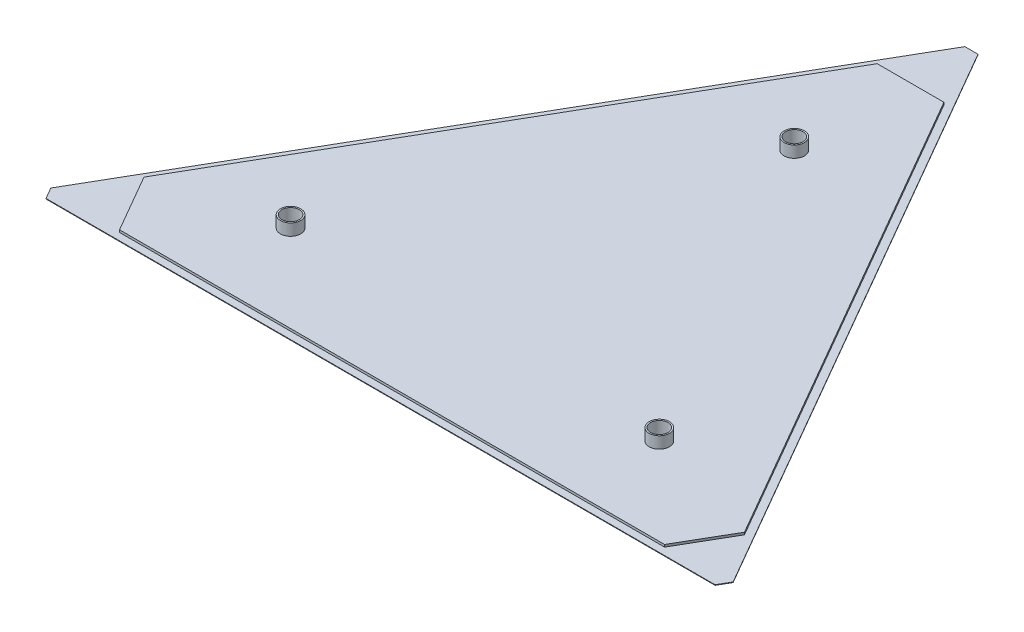
SolidWorks part; units mm, degrees
ref_plane "Front Plane" through (0, 0, 0) normal (0, 0, 1) x (1, 0, 0)
ref_plane "Top Plane" through (0, 0, 0) normal (0, 1, 0) x (1, 0, 0)
ref_plane "Right Plane" through (0, 0, 0) normal (1, 0, 0) x (0, 0, -1)
sketch "Sketch1" plane through (0, 0, 0) normal (0, 1, 0) x (1, 0, 0)
  line L1 (347.2736, 23.6092) -> (347.2736, 3.6092) construction
  line L2 (428.1137, -116.4172) -> (410.7932, -106.4172) construction
  line L8 (243.3042, -116.4848) -> (254.8093, -136.4089)
  line L10 (266.4391, -116.428) -> (283.7585, -106.4261) construction
  line L13 (452.6999, -118.9847) -> (442.6021, -136.4093)
  line L19 (231.9812, -138.9144) -> (229.7127, -134.9863)
  line L21 (344.9807, 64.6634) -> (229.7127, -134.9863)
  line L22 (349.5168, 64.6634) -> (344.9807, 64.6634)
  line L27 (464.7848, -134.9867) -> (462.5171, -138.9144)
  line L28 (462.5171, -138.9144) -> (231.9812, -138.9144)
  line L35 (335.7675, 43.666) -> (243.3042, -116.4848)
  line L36 (358.7782, 43.666) -> (335.7675, 43.666)
  line L62 (452.6999, -118.9847) -> (358.7782, 43.666)
  line L63 (442.6021, -136.4093) -> (254.8093, -136.4089)
  line L69 (464.7848, -134.9867) -> (349.5168, 64.6634)
  circle A1 centre (347.2736, 3.6092) radius 1.5
  circle A2 centre (283.7585, -106.4261) radius 1.5
  circle A3 centre (410.7932, -106.4172) radius 1.5
  circle A4 centre (347.2736, 3.6092) radius 3
  circle A5 centre (410.7932, -106.4172) radius 3
  circle A6 centre (283.7585, -106.4261) radius 3
  circle A7 centre (347.2736, 3.6092) radius 3.5
  circle A8 centre (410.7932, -106.4172) radius 3.5
  circle A9 centre (283.7585, -106.4261) radius 3.5
  dimension "D1" = 20
  dimension "D2" = 3
  dimension "D5" = 3
  dimension "D6" = 3
  dimension "D7" = 6
  dimension "D8" = 6
  dimension "D9" = 6
  dimension "D10" = 7
  dimension "D11" = 7
  dimension "D12" = 7
  dimension "D3" = 20
  dimension "D4" = 20
extrude "Boss-Extrude1" add sketch "Sketch1" along normal blind 0.2 contours A6 | A4 | A2 | A5 | A3 | A1 | L69 L22 L21 L19 L28 L27 | L8 L63 L13 L62 L36 L35
extrude "Boss-Extrude2" add sketch "Sketch1<14>" along normal blind 1 contours L63 L13 L62 L36 L35 L8 | A9 A8 A7 region at (347.5163, 0, 69.8796)
sketch "Sketch1<14>" plane through (0, 0, 0) normal (0, 1, 0) x (1, 0, 0) same geometry as "Sketch1"
extrude "Boss-Extrude4" add sketch "Sketch1<17>" along normal blind 5 contours A9 A6 | A8 A5 | A7 A4 region at (343.8726, 0, -3.6092) region at (407.3921, 0, 106.4172) region at (280.3575, 0, 106.4261)
sketch "Sketch1<17>" plane through (0, 0, 0) normal (0, 1, 0) x (1, 0, 0) same geometry as "Sketch1"
